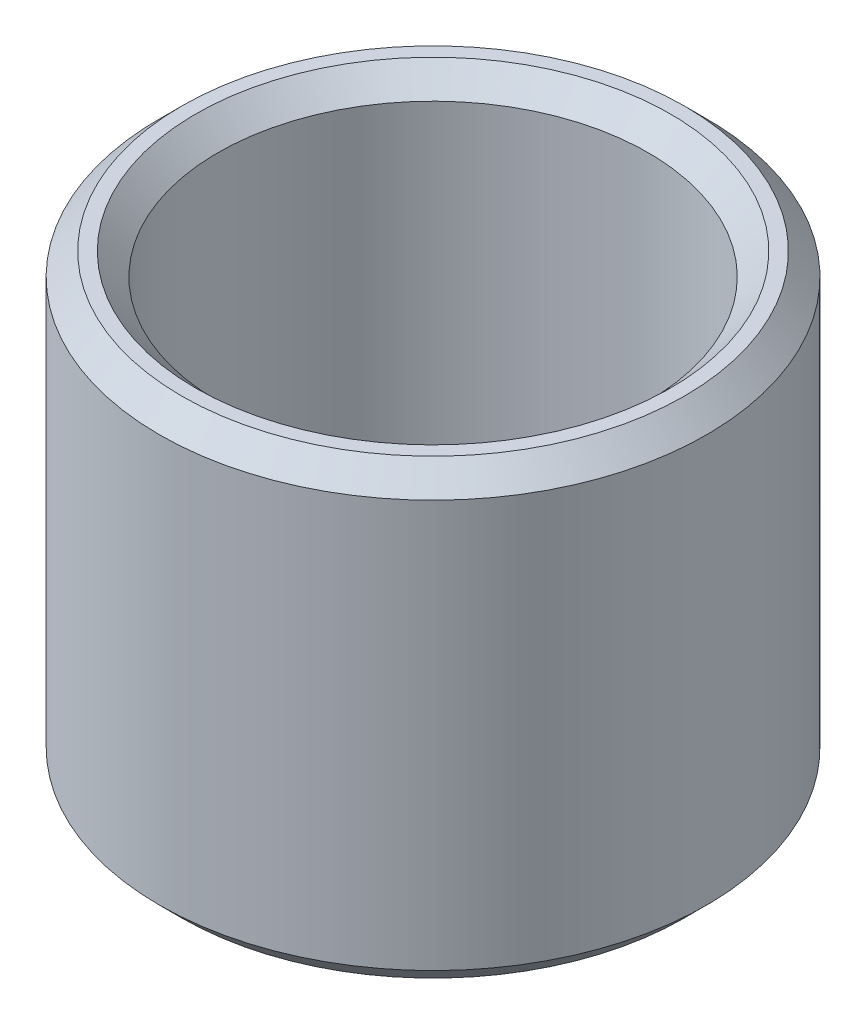
SolidWorks part; units mm, degrees
ref_plane "Front Plane" through (0, 0, 0) normal (0, 0, 1) x (1, 0, 0)
ref_plane "Top Plane" through (0, 0, 0) normal (0, 1, 0) x (1, 0, 0)
ref_plane "Right Plane" through (0, 0, 0) normal (1, 0, 0) x (0, 0, -1)
sketch "Sketch1" plane through (0, 0, 0) normal (0, 1, 0) x (1, 0, 0)
  circle A0 centre (0, 0) radius 40
  dimension "SLEEVE_OD" = 80
extrude "Boss-Extrude1" add sketch "Sketch1" along normal blind 66.0765
sketch "Sketch2" plane through (0, 0, 0) normal (0, 1, 0) x (1, 0, 0)
  circle A0 centre (0, 0) radius 31.4476
  dimension "BORE_D" = 62.8951
extrude "Cut-Extrude1" cut sketch "Sketch2" along normal through all
chamfer "Chamfer1" distance 3.2619 angle 45 4 edges at (0, 66.0765, 31.4476) (0, 0, 31.4476) (0, 0, 40) (0, 66.0765, 40)
